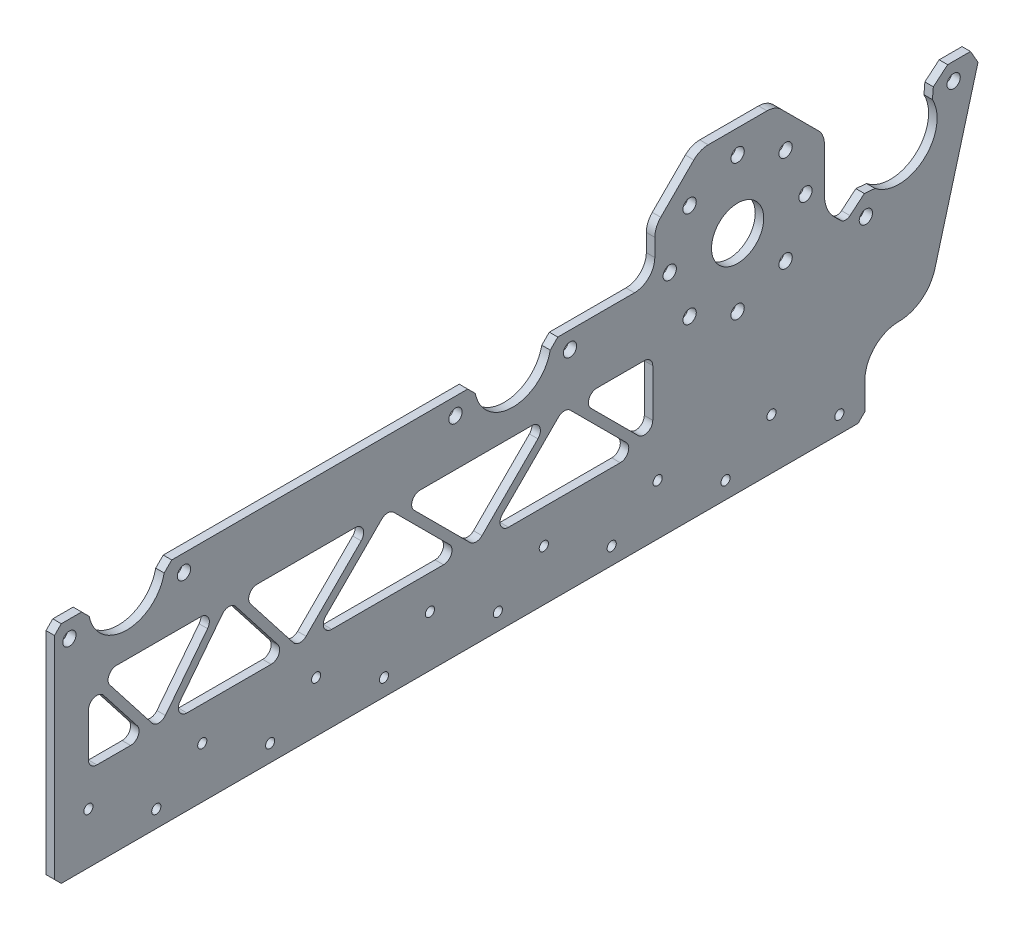
SolidWorks part; units mm, degrees
material "6061 Alloy"
ref_plane "Front Plane" through (0, 0, 0) normal (0, 0, 1) x (1, 0, 0)
ref_plane "Top Plane" through (0, 0, 0) normal (0, 1, 0) x (1, 0, 0)
ref_plane "Right Plane" through (0, 0, 0) normal (1, 0, 0) x (0, 0, -1)
sketch "Sketch1" plane through (0, 0, 0) normal (1, 0, 0) x (0, 0, -1)
  line L0 (-12.7, -12.7) -> (-315.9379, -12.7)
  line L1 (-315.9379, -12.7) -> (-315.9379, 71.4629)
  line L2 (-315.9379, 71.4629) -> (-303.2379, 71.4629)
  line L3 (-274.6121, 71.4629) -> (-158.7754, 71.4629)
  line L5 (10.9643, 80.6631) -> (18.2626, 86.7871)
  line L7 (-315.9379, 12.7) -> (13.4731, 12.7) construction
  line L8 (-12.7, -12.7) -> (-12.7, 0)
  line L9 (0, 12.4079) -> (0, 12.7) construction
  line L10 (13.4731, 22.9772) -> (30.9626, 86.7871)
  line L12 (-10.9643, 62.2627) -> (10.9643, 80.6631) construction
  line L13 (18.2626, 86.7871) -> (30.9626, 86.7871)
  line L14 (-130.1496, 71.4629) -> (-91.313, 71.4629)
  line L15 (-10.9643, 62.2627) -> (-18.2626, 56.1387)
  line L16 (-21.6532, 56.2511) -> (-23.945, 58.4485)
  line L18 (0, 71.4629) -> (-144.4625, 71.4629) construction
  line L19 (-315.9379, 15.875) -> (13.4731, 15.875) construction
  line L20 (-27.8553, 67.6154) -> (-27.8553, 87.307)
  line L21 (-27.8553, 87.307) -> (-46.1742, 105.6259)
  line L22 (-46.1742, 105.6259) -> (-74.4758, 105.6259)
  line L23 (-91.313, 88.7887) -> (-91.313, 71.4629)
  line L25 (-74.4758, 105.6259) -> (-91.313, 88.7887)
  line L26 (-144.4625, 71.4629) -> (-288.925, 71.4629) construction
  arc A3 (0, 12.7) -> (13.4731, 22.9772) centre (0, 26.67) ccw
  arc A4 (0, 12.7) -> (-12.7, 0) centre (0, 0) ccw
  circle A5 centre (0, 0) radius 12.4079 construction
  arc A6 (-303.2379, 71.4629) -> (-274.6121, 71.4629) centre (-288.925, 71.4629) ccw
  arc A7 (-158.7754, 71.4629) -> (-130.1496, 71.4629) centre (-144.4625, 71.4629) ccw
  arc A8 (-10.9643, 62.2627) -> (10.9643, 80.6631) centre (0, 71.4629) ccw
  arc A9 (-18.2626, 56.1387) -> (-21.6532, 56.2511) centre (-19.8953, 58.0845) cw
  circle A11 centre (-60.325, 71.4629) radius 9.779
  arc A14 (-27.8553, 67.6154) -> (-23.945, 58.4485) centre (-15.1553, 67.6154) ccw
  circle A15 centre (-60.325, 71.4629) radius 25.4 construction
  circle A16 centre (-60.325, 96.8629) radius 2.413
  circle A17 centre (-42.3645, 89.4234) radius 2.413
  circle A18 centre (-34.925, 71.4629) radius 2.413
  circle A19 centre (-42.3645, 53.5024) radius 2.413
  circle A20 centre (-60.325, 46.0629) radius 2.413
  circle A21 centre (-78.2855, 53.5024) radius 2.413
  circle A22 centre (-85.725, 71.4629) radius 2.413
  circle A23 centre (-78.2855, 89.4234) radius 2.413
  point P4 (-164.319, -12.7)
  point P44 (-82.018, 71.4629)
  point P51 (-27.8553, 62.1979)
  point P60 (-60.325, 71.4629)
  dimension "D1" = 25.4
  dimension "D3" = 12.7
  dimension "D5" = 28.6258
  dimension "D6" = 3.175
  dimension "D7" = 13.97
  dimension "D8" = 12.7
  dimension "D10" = 24.8158
  dimension "D13" = 9.5273
  dimension "D14" = 140
  dimension "D15" = 2.54
  dimension "D16" = 50.8
  dimension "D17" = 60.325
  dimension "D18" = 41.275
  dimension "D24" = 3.175
  dimension "D26" = 12.7
  dimension "D19" = 4.826
  dimension "D25" = 6.35
  dimension "D29" = 6.35
  dimension "D20" = 4.6567
  dimension "D30" = 9.779
  dimension "D2" = 0
  dimension "D4" = 12.7
  dimension "D9" = 12.7
  dimension "D11" = 288.925
  dimension "D12" = 288.925
  dimension "D21" = 8
  dimension "D22" = 45
  dimension "D23" = 45
  dimension "D27" = 6.35
  dimension "D28" = 3.175
extrude "Boss-Extrude1" add sketch "Sketch1" along normal blind 3.175
hole_wizard "#10 Clearance Hole1" positions "Sketch2" profile "Sketch3" hole size "#10" standard "ANSI Inch" end condition through all
sketch "Sketch2" plane through (3.175, 0, 0) normal (1, 0, 0) x (0, 0, -1)
  line L0 (-310.3562, 65.1129) -> (-267.4937, 65.1129) construction
  line L2 (-165.8937, 65.1129) -> (-123.0313, 65.1129) construction
  line L4 (-12.3356, 52.8228) -> (20.499, 80.3743) construction
  line L6 (-303.2379, 71.4629) -> (-315.9379, 71.4629) construction
  line L7 (-288.925, 65.1129) -> (-288.925, 71.4629) construction
  line L9 (-144.4625, 71.4629) -> (-144.4625, 65.1129) construction
  line L11 (0, 71.4629) -> (4.0817, 66.5985) construction
  line L14 (18.2626, 86.7871) -> (10.9643, 80.6631) construction
  line L15 (18.2626, 86.7871) -> (10.9643, 80.6631) construction
  point P0 (-310.3562, 65.1129)
  point P2 (-267.4937, 65.1129)
  point P4 (-165.8937, 65.1129)
  point P6 (-123.0313, 65.1129)
  point P8 (-12.3356, 52.8228)
  point P10 (20.499, 80.3743)
  dimension "D1" = 42.8625
  dimension "D2" = 6.35
  dimension "D3" = 6.35
sketch "Sketch3" plane through (3.175, 65.1129, 310.3562) normal (0, 1, 0) x (0, 0, -1)
  line L0 (0, 0) -> (0, 3.175)
  line L1 (0, 3.175) -> (2.4892, 3.175)
  line L2 (2.4892, 3.175) -> (2.4892, 0)
  line L5 (2.4892, 0) -> (0, 0)
  line L11 (0, -6.35) -> (0, 107.95) construction
  dimension "Thru Hole Dia." = 4.9784
  dimension "Thru Hole Depth" = 3.175
hole_wizard "#10 Clearance Hole2" positions "Sketch5" profile "Sketch6" hole size "#10" standard "ANSI Inch"
sketch "Sketch5" plane through (3.175, 0, 0) normal (1, 0, 0) x (0, 0, -1)
  point P0 (-60.325, 96.8629)
  point P3 (-42.3645, 89.4234)
  point P6 (-34.925, 71.4629)
  point P9 (-42.3645, 53.5024)
  point P12 (-60.325, 46.0629)
  point P15 (-78.2855, 53.5024)
  point P18 (-85.725, 71.4629)
  point P21 (-78.2855, 89.4234)
sketch "Sketch6" plane through (3.175, 96.8629, 60.325) normal (0, 1, 0) x (0, 0, -1)
  line L0 (0, 0) -> (0, 4.6707)
  line L1 (0, 4.6707) -> (2.4892, 3.175)
  line L2 (2.4892, 3.175) -> (2.4892, 0)
  line L5 (2.4892, 0) -> (0, 0)
  line L10 (0, 4.6707) -> (-2.4892, 3.175) construction
  line L11 (0, -6.35) -> (0, 107.95) construction
  dimension "Hole Dia." = 4.9784
  dimension "Hole Depth" = 3.175
  dimension "Drill Angle" = 118
chamfer "Chamfer1" distance 5.08 angle 45 1 edges at (1.5875, 86.7871, -30.9626) first distance on face at (1.5875, 54.8821, -22.2179)
fillet "Fillet1" radius 7.62 5 edges at (1.5875, 87.307, 27.8553) (1.5875, 105.6259, 46.1742) (1.5875, 105.6259, 74.4758) (1.5875, 88.7887, 91.313) (1.5875, 71.4629, 91.313)
hole_wizard "1/8 (0.135) Diameter Hole1" positions "Sketch7" profile "Sketch8" hole size "1/8" standard "ANSI Inch"
sketch "Sketch7" plane through (0, 0, 0) normal (-1, 0, 0) x (0, 0, 1)
  line L0 (315.9379, -12.7) -> (12.7, -12.7) construction
  line L1 (12.7, -12.7) -> (12.7, 0) construction
  line L2 (315.9379, 71.4629) -> (315.9379, -12.7) construction
  point P0 (22.2504, -6.35)
  point P2 (47.6504, 6.35)
  point P19 (64.8483, -6.35)
  point P20 (90.2483, 6.35)
  point P21 (107.4462, -6.35)
  point P22 (132.8462, 6.35)
  point P23 (150.0441, -6.35)
  point P24 (175.4441, 6.35)
  point P25 (192.6421, -6.35)
  point P26 (218.0421, 6.35)
  point P27 (235.24, -6.35)
  point P28 (260.64, 6.35)
  point P29 (277.8379, -6.35)
  point P30 (303.2379, 6.35)
  dimension "D1" = 6.35
  dimension "D2" = 25.4
  dimension "D3" = 12.7
  dimension "D4" = 9.5504
  dimension "D6" = 12.7
  dimension "D5" = 7
sketch "Sketch8" plane through (0, -6.35, 22.2504) normal (0, 1, 0) x (0, 0, 1)
  line L0 (0, 0) -> (0, 17.5402)
  line L1 (0, 17.5402) -> (1.7145, 16.51)
  line L2 (1.7145, 16.51) -> (1.7145, 0)
  line L5 (1.7145, 0) -> (0, 0)
  line L10 (0, 17.5402) -> (-1.7145, 16.51) construction
  line L11 (0, -6.35) -> (0, 107.95) construction
  dimension "Hole Dia." = 3.429
  dimension "Hole Depth" = 16.51
  dimension "Drill Angle" = 118
sketch "Sketch9" plane through (3.175, 0, 0) normal (1, 0, 0) x (0, 0, -1)
  line L0 (-303.2379, 47.625) -> (-303.2379, 19.05)
  line L1 (-303.2379, 19.05) -> (-280.9628, 19.05)
  line L2 (-280.9628, 19.05) -> (-303.2379, 47.625)
  line L3 (-315.9379, 12.7) -> (-12.7, 12.7) construction
  line L4 (-315.9379, 15.875) -> (-12.7, 15.875) construction
  line L5 (-299.2122, 47.625) -> (-276.9371, 19.05)
  line L6 (-276.9371, 19.05) -> (-254.662, 47.625)
  line L7 (-254.662, 47.625) -> (-299.2122, 47.625)
  line L8 (-272.9114, 19.05) -> (-250.6363, 47.625)
  line L9 (-250.6363, 47.625) -> (-228.3612, 19.05)
  line L10 (-228.3612, 19.05) -> (-272.9114, 19.05)
  line L11 (-246.6106, 47.625) -> (-224.3355, 19.05)
  line L12 (-224.3355, 19.05) -> (-195.7605, 47.625)
  line L13 (-195.7605, 47.625) -> (-246.6106, 47.625)
  line L14 (-219.8454, 19.05) -> (-191.2704, 47.625)
  line L15 (-191.2704, 47.625) -> (-162.6954, 19.05)
  line L16 (-162.6954, 19.05) -> (-219.8454, 19.05)
  line L17 (-186.7803, 47.625) -> (-158.2053, 19.05)
  line L18 (-158.2053, 19.05) -> (-129.6303, 47.625)
  line L19 (-129.6303, 47.625) -> (-186.7803, 47.625)
  line L20 (-125.1401, 47.625) -> (-153.7151, 19.05)
  line L21 (-153.7151, 19.05) -> (-96.5651, 19.05)
  line L22 (-96.5651, 19.05) -> (-125.1401, 47.625)
  line L32 (-315.9379, -12.7) -> (-12.7, -12.7) construction
  line L33 (-315.9379, 71.4629) -> (-315.9379, -12.7) construction
  line L35 (-120.65, 47.625) -> (-92.075, 19.05)
  line L36 (-92.075, 19.05) -> (-92.075, 47.625)
  line L37 (-92.075, 47.625) -> (-120.65, 47.625)
  line L38 (-12.7, -12.7) -> (-12.7, 0) construction
  arc A0 (-303.2379, 71.4629) -> (-274.6121, 71.4629) centre (-288.925, 71.4629) ccw construction
  dimension "D1" = 3.175
  dimension "D2" = 3.175
  dimension "D3" = 3.175
  dimension "D4" = 3.175
  dimension "D5" = 3.175
  dimension "D6" = 3.175
  dimension "D7" = 3.175
  dimension "D8" = 79.375
  dimension "D9" = 3.175
  dimension "D11" = 25.4
  dimension "D12" = 3.175
  dimension "D13" = 12.7
  dimension "D15" = 9.525
extrude "Cut-Extrude1" cut sketch "Sketch9" against normal through all
fillet "Fillet2" radius 3.175 24 edges at (1.5875, 19.05, 303.2379) (1.5875, 47.625, 303.2379) (1.5875, 19.05, 280.9628) (1.5875, 19.05, 153.7151) (1.5875, 47.625, 125.1401) (1.5875, 19.05, 96.5651) (1.5875, 19.05, 158.2053) (1.5875, 47.625, 186.7803) (1.5875, 47.625, 129.6303) (1.5875, 19.05, 92.075) (1.5875, 47.625, 120.65) (1.5875, 47.625, 92.075) (1.5875, 47.625, 250.6363) (1.5875, 19.05, 228.3612) (1.5875, 19.05, 272.9114) (1.5875, 19.05, 276.9371) (1.5875, 47.625, 299.2122) (1.5875, 47.625, 254.662) (1.5875, 19.05, 162.6954) (1.5875, 19.05, 219.8454) (1.5875, 19.05, 224.3355) (1.5875, 47.625, 246.6106) (1.5875, 47.625, 195.7605) (1.5875, 47.625, 191.2704)
chamfer "Chamfer2" distance 2.54 angle 45 9 edges at (1.5875, -12.7, 12.7) (1.5875, -12.7, 315.9379) (1.5875, 71.4629, 315.9379) (1.5875, 80.6631, -10.9643) (1.5875, 62.2627, 10.9643) (1.5875, 71.4629, 130.1496) (1.5875, 71.4629, 158.7754) (1.5875, 71.4629, 274.6121) (1.5875, 71.4629, 303.2379)
